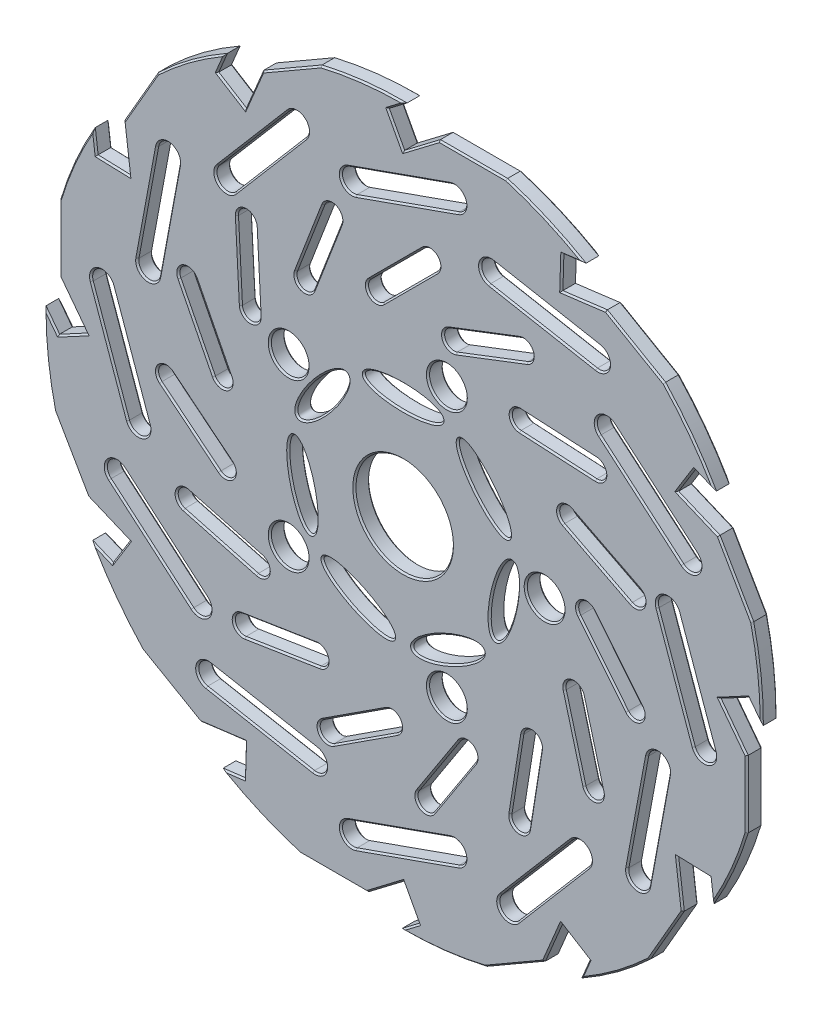
SolidWorks part; units mm, degrees
ref_plane "Front Plane" through (0, 0, 0) normal (0, 0, 1) x (1, 0, 0)
ref_plane "Top Plane" through (0, 0, 0) normal (0, 1, 0) x (1, 0, 0)
ref_plane "Right Plane" through (0, 0, 0) normal (1, 0, 0) x (0, 0, -1)
sketch "Sketch1" plane through (0, 0, 0) normal (0, 0, 1) x (1, 0, 0)
  circle A0 centre (0, 0) radius 31
  circle A1 centre (0, 0) radius 228.1007
extrude "Boss-Extrude1" add sketch "Sketch1" along normal mid plane 10
sketch "Sketch2" plane through (0, 0, 5) normal (0, 0, 1) x (1, 0, 0)
  line L0 (17.0698, 149.5996) -> (-17.0698, 115.46) construction
  line L1 (0, -55) -> (0, 55) construction
  line L2 (21.2802, 145.3892) -> (-12.8594, 111.2496)
  line L3 (12.8594, 153.81) -> (-21.2802, 119.6704)
  arc A0 (21.2802, 145.3892) -> (12.8594, 153.81) centre (17.0698, 149.5996) ccw
  arc A1 (-21.2802, 119.6704) -> (-12.8594, 111.2496) centre (-17.0698, 115.46) ccw
  point P4 (0, 132.5298)
extrude "Cut-Extrude1" cut sketch "Sketch2" against normal blind 36
ref_axis "Axis1" through (0, 0, 5.5) along (0, 0, -1)
pattern_circular "CirPattern1" count 15 over 360 about axis through (0, 0, 0) along (0, 0, 1) of "Cut-Extrude1"
sketch "Sketch3" plane through (0, 0, 5) normal (0, 0, 1) x (1, 0, 0)
  line L0 (0, -55) -> (0, 55) construction
  ellipse E0 centre (0, 65.6716) end of major axis (24.9934, 65.6716) minor radius 7.2851
extrude "Cut-Extrude2" cut sketch "Sketch3" against normal blind 36
pattern_circular "CirPattern2" count 7 over 360 about axis through (0, 0, 5.5) along (0, 0, -1) of "Cut-Extrude2"
sketch "Sketch4" plane through (0, 0, 5) normal (0, 0, 1) x (1, 0, 0)
  line L0 (32.5417, 191.4361) -> (-32.5417, 168.3809) construction
  line L1 (0, -5.5) -> (0, 5.5) construction
  line L2 (34.8868, 184.816) -> (-30.1966, 161.7608)
  line L3 (30.1966, 198.0562) -> (-34.8868, 175.001)
  line L4 (0, 201.2126) -> (22.7428, 218.4989)
  line L5 (22.7428, 218.4989) -> (76.6354, 218.4989)
  line L6 (76.6354, 218.4989) -> (-24.5402, 246.462)
  line L7 (-24.5402, 246.462) -> (4.957, 230.6743)
  line L8 (4.957, 230.6743) -> (-9.7916, 219.4642)
  line L9 (-9.7916, 219.4642) -> (0, 201.2126)
  arc A0 (34.8868, 184.816) -> (30.1966, 198.0562) centre (32.5417, 191.4361) ccw
  arc A1 (-34.8868, 175.001) -> (-30.1966, 161.7608) centre (-32.5417, 168.3809) ccw
  point P4 (0, 179.9085)
extrude "Cut-Extrude3" cut sketch "Sketch4" against normal blind 51
pattern_circular "CirPattern3" count 12 over 360 about axis through (0, 0, 0) along (0, 0, 1) of "Cut-Extrude3"
sketch "Sketch5" plane through (0, 0, 5) normal (0, 0, 1) x (1, 0, 0)
  line L0 (5.5, 0) -> (-5.5, 0) construction
  circle A0 centre (90, 0) radius 12
  dimension "D1" = 90
extrude "Cut-Extrude4" cut sketch "Sketch5" against normal blind 50
pattern_circular "CirPattern4" count 5 over 360 about axis through (0, 0, 0) along (0, 0, 1) of "Cut-Extrude4"
chamfer "Chamfer1" distance 1 angle 45 362 edges at (31, 0, -5) (-21.2802, 111.2496, -5) (-4.2104, 136.7402, -5) (21.2802, 153.81, -5) (4.2104, 128.3194, -5) (25.8088, 110.287, -5) (51.7708, 126.6309, -5) (82.0006, 131.857, -5) (56.0386, 115.513, -5) (68.4353, 90.2548, -5) (98.8004, 94.626, -5) (128.5423, 87.1047, -5) (98.1772, 82.7335, -5) (99.2287, 54.6167, -5) (128.7465, 46.2594, -5) (152.8579, 27.2912, -5) (123.3401, 35.6485, -5) (112.8645, 9.5349, -5) (136.4312, -10.1059, -5) (150.743, -37.2412, -5) (127.1763, -17.6004, -5) (106.9851, -37.1956, -5) (120.5257, -64.7238, -5) (122.5632, -95.3342, -5) (109.0226, -67.806, -5) (82.6069, -77.4946, -5) (83.7801, -108.1503, -5) (73.1912, -136.9431, -5) (72.0179, -106.2874, -5) (43.9453, -104.3941, -5) (32.5483, -132.8767, -5) (11.1637, -154.8733, -5) (22.5607, -126.3907, -5) (-2.3149, -113.2429, -5) (-24.3115, -134.6275, -5) (-52.7941, -146.0245, -5) (-30.7975, -124.6399, -5) (-48.1748, -102.511, -5) (-76.9676, -113.0999, -5) (-107.6233, -111.9267, -5) (-78.8305, -101.3377, -5) (-85.7048, -74.054, -5) (-116.3153, -72.0164, -5) (-143.8435, -58.4758, -5) (-113.233, -60.5134, -5) (-108.4157, -32.7924, -5) (-135.551, -18.4806, -5) (-155.1918, 5.0861, -5) (-128.0565, -9.2257, -5) (-112.3806, 14.1393, -5) (-131.3487, 38.2507, -5) (-139.706, 67.7686, -5) (-120.7379, 43.6572, -5) (-96.9138, 58.6262, -5) (-104.4351, 88.3681, -5) (-100.0639, 118.7332, -5) (-92.5426, 88.9914, -5) (-64.6897, 92.9761, -5) (-59.4636, 123.2058, -5) (-43.1197, 149.1679, -5) (-48.3458, 118.9381, -5) (24.9934, 65.6716, -5) (66.9272, 21.405, -5) (58.4635, -38.98, -5) (5.9756, -70.0123, -5) (-51.0121, -48.3238, -5) (-69.5866, 9.7534, -5) (-35.761, 60.4862, -5) (-39.1618, 166.0358, -5) (-2.3451, 186.5286, -5) (39.1618, 193.7812, -5) (2.3451, 173.2884, -5) (49.1028, 163.3721, -5) (91.2334, 162.711, -5) (130.8057, 148.2385, -5) (88.6751, 148.8996, -5) (124.2103, 116.933, -5) (160.3659, 95.2952, -5) (187.4003, 62.9755, -5) (151.2447, 84.6133, -5) (166.0358, 39.1618, -5) (186.5286, 2.3451, -5) (193.7812, -39.1618, -5) (173.2884, -2.3451, -5) (163.3721, -49.1028, -5) (162.711, -91.2334, -5) (148.2385, -130.8057, -5) (148.8996, -88.6751, -5) (116.933, -124.2103, -5) (95.2952, -160.3659, -5) (62.9755, -187.4003, -5) (84.6133, -151.2447, -5) (39.1618, -166.0358, -5) (2.3451, -186.5286, -5) (-39.1618, -193.7812, -5) (-2.3451, -173.2884, -5) (-49.1028, -163.3721, -5) (-91.2334, -162.711, -5) (-130.8057, -148.2385, -5) (-88.6751, -148.8996, -5) (-124.2103, -116.933, -5) (-160.3659, -95.2952, -5) (-187.4003, -62.9755, -5) (-151.2447, -84.6133, -5) (-166.0358, -39.1618, -5) (-186.5286, -2.3451, -5) (-193.7812, 39.1618, -5) (-173.2884, 2.3451, -5) (-163.3721, 49.1028, -5) (-162.711, 91.2334, -5) (-148.2385, 130.8057, -5) (-148.8996, 88.6751, -5) (-116.933, 124.2103, -5) (-95.2952, 160.3659, -5) (-62.9755, 187.4003, -5) (-84.6133, 151.2447, -5) (-167.1688, 147.4528, -5) (-176.0547, 114.7758, -5) (-184.6063, 100.9293, -5) (-195.8559, 108.3272, -5) (-209.1214, 91.0943, -5) (-218.4989, 44.1135, -5) (-209.8557, 11.3714, -5) (-210.3384, -4.8958, -5) (-223.7798, -4.1138, -5) (-226.6516, -25.6707, -5) (-211.2823, -71.046, -5) (-187.4261, -95.0799, -5) (-179.7105, -109.4091, -5) (-191.7421, -115.4525, -5) (-183.4507, -135.5573, -5) (-147.4528, -167.1688, -5) (-114.7758, -176.0547, -5) (-100.9293, -184.6063, -5) (-108.3272, -195.8559, -5) (-91.0943, -209.1214, -5) (-44.1135, -218.4989, -5) (-11.3714, -209.8557, -5) (4.8958, -210.3384, -5) (4.1138, -223.7798, -5) (25.6707, -226.6516, -5) (71.046, -211.2823, -5) (95.0799, -187.4261, -5) (109.4091, -179.7105, -5) (115.4525, -191.7421, -5) (135.5573, -183.4507, -5) (167.1688, -147.4528, -5) (176.0547, -114.7758, -5) (184.6063, -100.9293, -5) (195.8559, -108.3272, -5) (209.1214, -91.0943, -5) (218.4989, -44.1135, -5) (209.8557, -11.3714, -5) (210.3384, 4.8958, -5) (223.7798, 4.1138, -5) (226.6516, 25.6707, -5) (211.2823, 71.046, -5) (187.4261, 95.0799, -5) (179.7105, 109.4091, -5) (191.7421, 115.4525, -5) (183.4507, 135.5573, -5) (147.4528, 167.1688, -5) (114.7758, 176.0547, -5) (100.9293, 184.6063, -5) (108.3272, 195.8559, -5) (91.0943, 209.1214, -5) (44.1135, 218.4989, -5) (11.3714, 209.8557, -5) (-4.8958, 210.3384, -5) (-4.1138, 223.7798, -5) (-25.6707, 226.6516, -5) (-71.046, 211.2823, -5) (-95.0799, 187.4261, -5) (-109.4091, 179.7105, -5) (-115.4525, 191.7421, -5) (-135.5573, 183.4507, -5) (102, 0, -5) (39.8115, -85.5951, -5) (-60.8115, -52.9007, -5) (-60.8115, 52.9007, -5) (39.8115, 85.5951, -5) (31, 0, 5) (-4.2104, 136.7402, 5) (-21.2802, 111.2496, 5) (4.2104, 128.3194, 5) (21.2802, 153.81, 5) (51.7708, 126.6309, 5) (25.8088, 110.287, 5) (56.0386, 115.513, 5) (82.0006, 131.857, 5) (98.8004, 94.626, 5) (68.4353, 90.2548, 5) (98.1772, 82.7335, 5) (128.5423, 87.1047, 5) (128.7465, 46.2594, 5) (99.2287, 54.6167, 5) (123.3401, 35.6485, 5) (152.8579, 27.2912, 5) (136.4312, -10.1059, 5) (112.8645, 9.5349, 5) (127.1763, -17.6004, 5) (150.743, -37.2412, 5) (120.5257, -64.7238, 5) (106.9851, -37.1956, 5) (109.0226, -67.806, 5) (122.5632, -95.3342, 5) (83.7801, -108.1503, 5) (82.6069, -77.4946, 5) (72.0179, -106.2874, 5) (73.1912, -136.9431, 5) (32.5483, -132.8767, 5) (43.9453, -104.3941, 5) (22.5607, -126.3907, 5) (11.1637, -154.8733, 5) (-24.3115, -134.6275, 5) (-2.3149, -113.2429, 5) (-30.7975, -124.6399, 5) (-52.7941, -146.0245, 5) (-76.9676, -113.0999, 5) (-48.1748, -102.511, 5) (-78.8305, -101.3377, 5) (-107.6233, -111.9267, 5) (-116.3153, -72.0164, 5) (-85.7048, -74.054, 5) (-113.233, -60.5134, 5) (-143.8435, -58.4758, 5) (-135.551, -18.4806, 5) (-108.4157, -32.7924, 5) (-128.0565, -9.2257, 5) (-155.1918, 5.0861, 5) (-131.3487, 38.2507, 5) (-112.3806, 14.1393, 5) (-120.7379, 43.6572, 5) (-139.706, 67.7686, 5) (-104.4351, 88.3681, 5) (-96.9138, 58.6262, 5) (-92.5426, 88.9914, 5) (-100.0639, 118.7332, 5) (-59.4636, 123.2058, 5) (-64.6897, 92.9761, 5) (-48.3458, 118.9381, 5) (-43.1197, 149.1679, 5) (24.9934, 65.6716, 5) (66.9272, 21.405, 5) (58.4635, -38.98, 5) (5.9756, -70.0123, 5) (-51.0121, -48.3238, 5) (-69.5866, 9.7534, 5) (-35.761, 60.4862, 5) (-2.3451, 186.5286, 5) (-39.1618, 166.0358, 5) (2.3451, 173.2884, 5) (39.1618, 193.7812, 5) (91.2334, 162.711, 5) (49.1028, 163.3721, 5) (88.6751, 148.8996, 5) (130.8057, 148.2385, 5) (160.3659, 95.2952, 5) (124.2103, 116.933, 5) (151.2447, 84.6133, 5) (187.4003, 62.9755, 5) (186.5286, 2.3451, 5) (166.0358, 39.1618, 5) (173.2884, -2.3451, 5) (193.7812, -39.1618, 5) (162.711, -91.2334, 5) (163.3721, -49.1028, 5) (148.8996, -88.6751, 5) (148.2385, -130.8057, 5) (95.2952, -160.3659, 5) (116.933, -124.2103, 5) (84.6133, -151.2447, 5) (62.9755, -187.4003, 5) (2.3451, -186.5286, 5) (39.1618, -166.0358, 5) (-2.3451, -173.2884, 5) (-39.1618, -193.7812, 5) (-91.2334, -162.711, 5) (-49.1028, -163.3721, 5) (-88.6751, -148.8996, 5) (-130.8057, -148.2385, 5) (-160.3659, -95.2952, 5) (-124.2103, -116.933, 5) (-151.2447, -84.6133, 5) (-187.4003, -62.9755, 5) (-186.5286, -2.3451, 5) (-166.0358, -39.1618, 5) (-173.2884, 2.3451, 5) (-193.7812, 39.1618, 5) (-162.711, 91.2334, 5) (-163.3721, 49.1028, 5) (-148.8996, 88.6751, 5) (-148.2385, 130.8057, 5) (-95.2952, 160.3659, 5) (-116.933, 124.2103, 5) (-84.6133, 151.2447, 5) (-62.9755, 187.4003, 5) (-109.4091, 179.7105, 5) (-95.0799, 187.4261, 5) (-71.046, 211.2823, 5) (-25.6707, 226.6516, 5) (-4.1138, 223.7798, 5) (-4.8958, 210.3384, 5) (11.3714, 209.8557, 5) (44.1135, 218.4989, 5) (91.0943, 209.1214, 5) (108.3272, 195.8559, 5) (100.9293, 184.6063, 5) (114.7758, 176.0547, 5) (147.4528, 167.1688, 5) (183.4507, 135.5573, 5) (191.7421, 115.4525, 5) (179.7105, 109.4091, 5) (187.4261, 95.0799, 5) (211.2823, 71.046, 5) (226.6516, 25.6707, 5) (223.7798, 4.1138, 5) (210.3384, 4.8958, 5) (209.8557, -11.3714, 5) (218.4989, -44.1135, 5) (209.1214, -91.0943, 5) (195.8559, -108.3272, 5) (184.6063, -100.9293, 5) (176.0547, -114.7758, 5) (167.1688, -147.4528, 5) (135.5573, -183.4507, 5) (115.4525, -191.7421, 5) (109.4091, -179.7105, 5) (95.0799, -187.4261, 5) (71.046, -211.2823, 5) (25.6707, -226.6516, 5) (4.1138, -223.7798, 5) (4.8958, -210.3384, 5) (-11.3714, -209.8557, 5) (-44.1135, -218.4989, 5) (-91.0943, -209.1214, 5) (-108.3272, -195.8559, 5) (-100.9293, -184.6063, 5) (-114.7758, -176.0547, 5) (-147.4528, -167.1688, 5) (-183.4507, -135.5573, 5) (-191.7421, -115.4525, 5) (-179.7105, -109.4091, 5) (-187.4261, -95.0799, 5) (-211.2823, -71.046, 5) (-226.6516, -25.6707, 5) (-223.7798, -4.1138, 5) (-210.3384, -4.8958, 5) (-209.8557, 11.3714, 5) (-218.4989, 44.1135, 5) (-209.1214, 91.0943, 5) (-195.8559, 108.3272, 5) (-184.6063, 100.9293, 5) (-176.0547, 114.7758, 5) (-167.1688, 147.4528, 5) (-135.5573, 183.4507, 5) (-115.4525, 191.7421, 5) (102, 0, 5) (31.5197, -97.0078, 5) (-82.5197, -59.9541, 5) (-82.5197, 59.9541, 5) (31.5197, 97.0078, 5)
